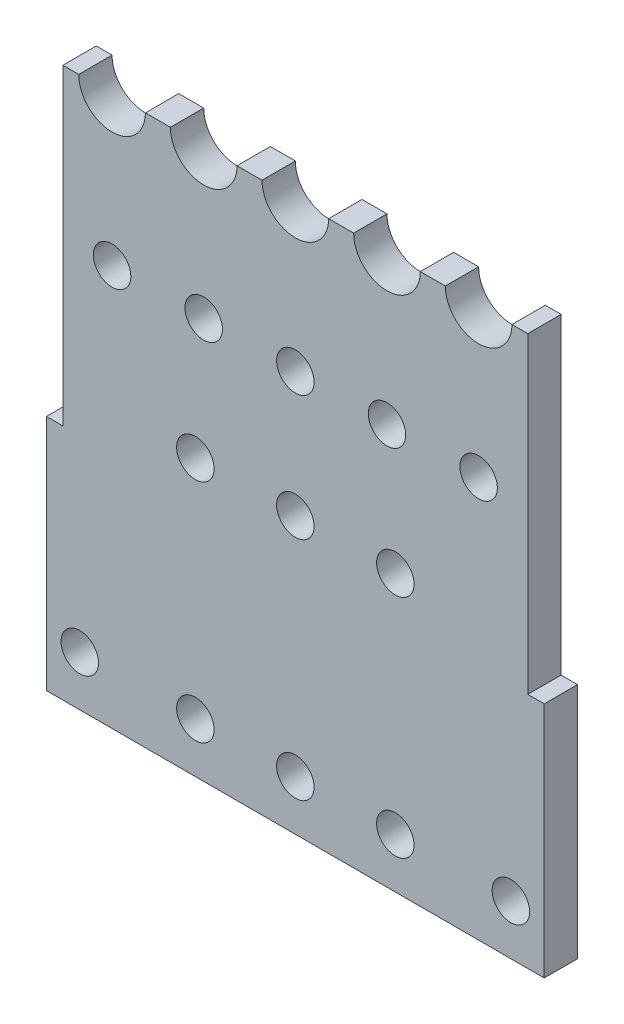
SolidWorks part; units mm, degrees
ref_plane "Спереди" through (0, 0, 0) normal (0, 0, 1) x (1, 0, 0)
ref_plane "Сверху" through (0, 0, 0) normal (0, 1, 0) x (1, 0, 0)
ref_plane "Справа" through (0, 0, 0) normal (1, 0, 0) x (0, 0, -1)
sketch "Эскиз1" plane through (0, 0, 0) normal (0, 0, 1) x (1, 0, 0)
  line L1 (-5.975, 6.6) -> (5.975, 6.6)
  line L2 (-5.975, 6.6) -> (-5.975, -6.6)
  line L3 (-5.975, -6.6) -> (5.975, -6.6)
  line L4 (5.975, 6.6) -> (5.975, -6.6)
  line L5 (-5.975, 6.6) -> (5.975, -6.6) construction
  line L6 (-5.975, -6.6) -> (5.975, 6.6) construction
  point P0 (0, 0)
  dimension "D1" = 11.95
  dimension "D2" = 13.2
extrude "Бобышка-Вытянуть1" add sketch "Эскиз1" along normal blind 0.8
sketch "Эскиз2" plane through (0, 0, 0.8) normal (0, 0, 1) x (1, 0, 0)
  line L0 (-5.975, -6.6) -> (5.975, -6.6) construction
  line L1 (-5.975, 6.6) -> (-5.58, 6.6)
  line L2 (-5.975, 6.6) -> (-5.975, -0.9)
  line L3 (-5.975, -0.9) -> (-5.58, -0.9)
  line L4 (-5.58, 6.6) -> (-5.58, -0.9)
  line L5 (5.975, 6.6) -> (5.58, 6.6)
  line L6 (5.975, 6.6) -> (5.975, -0.9)
  line L7 (5.975, -0.9) -> (5.58, -0.9)
  line L8 (5.58, 6.6) -> (5.58, -0.9)
  dimension "D1" = 11.16
  dimension "D2" = 5.7
extrude "Вырез-Вытянуть1" cut sketch "Эскиз2" against normal up to surface (0.8 mm away) up to face at (0, 0, 0)
sketch "Эскиз3" plane through (0, 0, 0.8) normal (0, 0, 1) x (1, 0, 0)
  line L0 (5.58, 6.6) -> (-5.58, 6.6) construction
  line L1 (-5.2, 6.6) -> (-3.6, 6.6)
  line L2 (-3, 6.6) -> (-1.4, 6.6)
  line L3 (-0.8, 6.6) -> (0.8, 6.6)
  line L4 (1.4, 6.6) -> (3, 6.6)
  line L5 (3.6, 6.6) -> (5.2, 6.6)
  arc A0 (-5.2, 6.6) -> (-3.6, 6.6) centre (-4.4, 6.6) ccw
  arc A1 (-3, 6.6) -> (-1.4, 6.6) centre (-2.2, 6.6) ccw
  arc A2 (-0.8, 6.6) -> (0.8, 6.6) centre (0, 6.6) ccw
  arc A3 (1.4, 6.6) -> (3, 6.6) centre (2.2, 6.6) ccw
  arc A4 (3.6, 6.6) -> (5.2, 6.6) centre (4.4, 6.6) ccw
  dimension "D5" = 0.8
  dimension "D1" = 0.6
  dimension "D2" = 0.6
  dimension "D3" = 0.6
  dimension "D4" = 0.6
extrude "Вырез-Вытянуть2" cut sketch "Эскиз3" against normal up to surface (0.8 mm away) up to face at (0, -0.45, 0)
sketch "Эскиз4" plane through (0, 0, 0.8) normal (0, 0, 1) x (1, 0, 0)
  line L0 (-5.975, -6.6) -> (5.975, -6.6) construction
  line L1 (-5.975, -0.9) -> (-5.975, -6.6) construction
  line L2 (5.975, -6.6) -> (5.975, -0.9) construction
  line L3 (-4.4, 5.8) -> (-4.4, 3.025) construction
  line L4 (-2.2, 5.8) -> (-2.2, 3.025) construction
  line L5 (2.2, 5.8) -> (2.2, 3.025) construction
  line L6 (4.4, 5.8) -> (4.4, 3.025) construction
  circle A0 centre (-2.4, -5.4) radius 0.45
  circle A1 centre (0, -5.4) radius 0.45
  circle A2 centre (2.4, -5.4) radius 0.45
  circle A3 centre (-2.4, 0.025) radius 0.45
  circle A4 centre (0, 0.025) radius 0.45
  circle A5 centre (2.4, 0.025) radius 0.45
  circle A6 centre (-5.175, -5.4) radius 0.45
  circle A7 centre (5.175, -5.4) radius 0.45
  circle A8 centre (-4.4, 3.025) radius 0.45
  circle A9 centre (-2.2, 3.025) radius 0.45
  circle A10 centre (0, 3.025) radius 0.45
  circle A11 centre (2.2, 3.025) radius 0.45
  circle A12 centre (4.4, 3.025) radius 0.45
  arc A13 (-5.2, 6.6) -> (-3.6, 6.6) centre (-4.4, 6.6) ccw construction
  arc A14 (-3, 6.6) -> (-1.4, 6.6) centre (-2.2, 6.6) ccw construction
  arc A15 (1.4, 6.6) -> (3, 6.6) centre (2.2, 6.6) ccw construction
  arc A16 (3.6, 6.6) -> (5.2, 6.6) centre (4.4, 6.6) ccw construction
  dimension "D1" = 0.9
  dimension "D2" = 2.4
  dimension "D3" = 2.4
  dimension "D4" = 1.2
  dimension "D5" = 5.425
  dimension "D6" = 0.8
  dimension "D7" = 0.8
  dimension "D8" = 3
extrude "Вырез-Вытянуть3" cut sketch "Эскиз4" against normal up to surface (0.8 mm away) up to face at (0, 3.2444, 0)
sketch "Эскиз5" plane through (0, 0, 0) normal (0, 0, -1) x (-1, 0, 0)
  line L0 (-5.5114, 2.1) -> (-5.5114, -3.4)
  line L1 (-5.5114, -3.4) -> (-2.9, -3.4)
  line L2 (-2.9, -3.4) -> (-2.9, -4.841)
  line L3 (-5.5114, 2.1) -> (-5.1125, 2.7909)
  line L4 (-4.5114, 1.8321) -> (-4.5114, -2.4)
  line L5 (-4.5114, -2.4) -> (-1.9, -2.4)
  line L6 (-1.9, -2.4) -> (-1.9, -4.841)
  line L7 (-4.5114, 1.8321) -> (-4.2465, 2.2909)
  line L8 (-0.5, -0.534) -> (-0.5, -4.841)
  line L9 (0.5, -0.534) -> (0.5, -4.841)
  line L10 (-2.7361, 2.5005) -> (-2.8617, 0.616)
  line L11 (-1.7383, 2.434) -> (-1.8639, 0.5495)
  line L12 (-0.5, 2.466) -> (-0.5, 0.584)
  line L13 (0.5, 0.584) -> (0.5, 2.466)
  line L14 (1.7383, 2.434) -> (1.8639, 0.5495)
  line L15 (2.7361, 2.5005) -> (2.8617, 0.616)
  line L16 (5.5114, 2.1) -> (5.5114, -3.4)
  line L17 (5.5114, -3.4) -> (2.9, -3.4)
  line L18 (2.9, -3.4) -> (2.9, -4.841)
  line L19 (5.5114, 2.1) -> (5.1125, 2.7909)
  line L20 (4.2465, 2.2909) -> (4.5114, 1.8321)
  line L21 (4.5114, 1.8321) -> (4.5114, -2.4)
  line L22 (4.5114, -2.4) -> (1.9, -2.4)
  line L23 (1.9, -2.4) -> (1.9, -4.841)
  arc A0 (-4.2465, 2.2909) -> (-5.1125, 2.7909) centre (-4.4, 3.025) ccw
  arc A1 (-1.7383, 2.434) -> (-2.7361, 2.5005) centre (-2.2, 3.025) ccw
  arc A2 (0.5, 2.466) -> (-0.5, 2.466) centre (0, 3.025) ccw
  arc A3 (2.7361, 2.5005) -> (1.7383, 2.434) centre (2.2, 3.025) ccw
  arc A4 (5.1125, 2.7909) -> (4.2465, 2.2909) centre (4.4, 3.025) ccw
  arc A5 (1.8639, 0.5495) -> (2.8617, 0.616) centre (2.4, 0.025) ccw
  arc A6 (-2.8617, 0.616) -> (-1.8639, 0.5495) centre (-2.4, 0.025) ccw
  arc A7 (0.5, -0.534) -> (0.5, 0.584) centre (0, 0.025) ccw
  arc A8 (-2.9, -4.841) -> (-1.9, -4.841) centre (-2.4, -5.4) ccw
  arc A9 (-0.5, -4.841) -> (0.5, -4.841) centre (0, -5.4) ccw
  arc A10 (1.9, -4.841) -> (2.9, -4.841) centre (2.4, -5.4) ccw
  circle A11 centre (-4.4, 3.025) radius 0.45 construction
  circle A12 centre (-4.4, 3.025) radius 0.45
  circle A13 centre (-2.4, -5.4) radius 0.45 construction
  circle A14 centre (-2.4, -5.4) radius 0.45
  circle A15 centre (0, 0.025) radius 0.45 construction
  circle A16 centre (0, 0.025) radius 0.45
  circle A17 centre (0, -5.4) radius 0.45 construction
  circle A18 centre (0, -5.4) radius 0.45
  arc A19 (-0.5, 0.584) -> (-0.5, -0.534) centre (0, 0.025) ccw
  circle A20 centre (0, 3.025) radius 0.45 construction
  circle A21 centre (0, 3.025) radius 0.45
  circle A22 centre (-2.4, 0.025) radius 0.45 construction
  circle A23 centre (-2.2, 3.025) radius 0.45 construction
  circle A24 centre (-2.4, 0.025) radius 0.45
  circle A25 centre (-2.2, 3.025) radius 0.45
  circle A26 centre (2.4, 0.025) radius 0.45 construction
  circle A27 centre (2.2, 3.025) radius 0.45 construction
  circle A28 centre (2.4, 0.025) radius 0.45
  circle A29 centre (2.2, 3.025) radius 0.45
  circle A30 centre (4.4, 3.025) radius 0.45 construction
  circle A31 centre (4.4, 3.025) radius 0.45
  circle A32 centre (2.4, -5.4) radius 0.45 construction
  circle A33 centre (2.4, -5.4) radius 0.45
  dimension "D1" = 1.5
  dimension "D2" = 1
  dimension "D3" = 1
  dimension "D4" = 1
  dimension "D5" = 0.5
  dimension "D6" = 2
  dimension "D7" = 1
  dimension "D8" = 150
  dimension "D9" = 0.5
  dimension "D10" = 5.5
  dimension "D11" = 1
  dimension "D12" = 0.5
  dimension "D13" = 0.5
  dimension "D14" = 0.5
  dimension "D15" = 1
  dimension "D16" = 0.5
  dimension "D17" = 0.5
  dimension "D18" = 1
  dimension "D19" = 0.5
  dimension "D20" = 1
  dimension "D21" = 1
  dimension "D22" = 1
  dimension "D23" = 0.5
  dimension "D24" = 1
split line "Разделяющая линия1"
